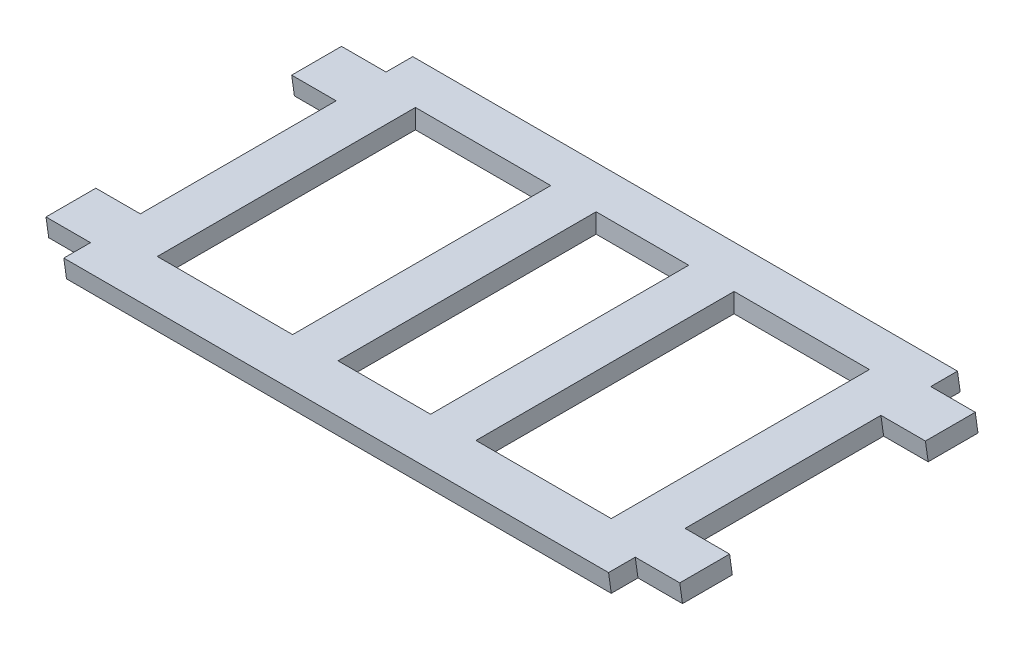
SolidWorks part; units mm, degrees
material "Balsa"
ref_plane "Front Plane" through (0, 0, 0) normal (0, 0, 1) x (1, 0, 0)
ref_plane "Top Plane" through (0, 0, 0) normal (0, 1, 0) x (1, 0, 0)
ref_plane "Right Plane" through (0, 0, 0) normal (1, 0, 0) x (0, 0, -1)
sketch "Sketch1" plane through (0, 0, 0) normal (0, 1, 0) x (1, 0, 0)
  line L4 (0, 0) -> (0, 7.112) construction
  line L5 (0, 7.112) -> (6.35, 7.112)
  line L6 (6.35, 7.112) -> (6.35, 35.052)
  line L7 (6.35, 35.052) -> (0, 35.052)
  line L8 (0, 7.112) -> (0, 0)
  line L10 (6.35, 7.112) -> (84.074, 7.112) construction
  line L11 (84.074, 7.112) -> (90.424, 7.112)
  line L12 (84.074, 7.112) -> (84.074, 35.052)
  line L13 (84.074, 35.052) -> (90.424, 35.052)
  line L15 (90.424, 7.112) -> (90.424, 0)
  line L16 (0, 35.052) -> (0, 42.164)
  line L18 (90.424, 42.164) -> (90.424, 35.052)
  line L19 (0, 42.164) -> (6.35, 42.164)
  line L20 (6.35, 42.164) -> (6.35, 45.974)
  line L21 (90.424, 42.164) -> (84.074, 42.164)
  line L22 (84.074, 42.164) -> (84.074, 45.974)
  line L23 (6.35, 45.974) -> (84.074, 45.974)
  line L24 (0, 0) -> (6.35, 0)
  line L25 (6.35, 0) -> (6.35, -3.81)
  line L26 (90.424, 0) -> (84.074, 0)
  line L27 (84.074, 0) -> (84.074, -3.81)
  line L28 (6.35, -3.81) -> (84.074, -3.81)
  dimension "D1" = 7.112
  dimension "D2" = 90.424
  dimension "D3" = 6.35
  dimension "D4" = 27.94
  dimension "D5" = 77.724
  dimension "D6" = 6.35
  dimension "D7" = 27.94
  dimension "D8" = 7.112
  dimension "D9" = 6.35
  dimension "D10" = 3.81
  dimension "D11" = 6.35
  dimension "D12" = 3.81
  dimension "D13" = 6.35
  dimension "D14" = 3.81
  dimension "D15" = 6.35
  dimension "D16" = 3.81
ref_plane "Plane1" through (0, 2.7668, 0) normal (0, 1, 0) x (1, 0, 0)
sketch "Sketch2" plane through (0, 2.7668, 0) normal (0, 1, 0) x (1, 0, 0)
  line L0 (0, 0) -> (0, -0.3888) construction
  line L2 (90.424, -0.3888) -> (90.424, 6.7232)
  line L3 (90.424, 7.112) -> (90.424, 0) construction
  line L4 (90.424, 6.7232) -> (84.074, 6.7232)
  line L5 (84.074, 6.7232) -> (84.074, 34.6632)
  line L6 (84.074, 7.112) -> (84.074, 35.052) construction
  line L7 (84.074, 34.6632) -> (90.424, 34.6632)
  line L8 (90.424, 34.6632) -> (90.424, 41.7752)
  line L9 (90.424, 42.164) -> (90.424, 35.052) construction
  line L11 (0, 35.052) -> (0, 42.164) construction
  line L12 (0, 41.7752) -> (0, 34.6632)
  line L13 (0, 34.6632) -> (6.35, 34.6632)
  line L14 (6.35, 7.112) -> (6.35, 35.052) construction
  line L15 (6.35, 34.6632) -> (6.35, 6.7232)
  line L16 (6.35, 6.7232) -> (0, 6.7232)
  line L17 (0, 7.112) -> (0, 0) construction
  line L18 (0, 6.7232) -> (0, -0.3888)
  line L19 (0, -0.3888) -> (6.35, -0.3888)
  line L20 (6.35, 0) -> (6.35, -3.81) construction
  line L21 (6.35, -0.3888) -> (6.35, -4.1988)
  line L22 (90.424, -0.3888) -> (84.074, -0.3888)
  line L23 (84.074, 0) -> (84.074, -3.81) construction
  line L24 (84.074, -0.3888) -> (84.074, -4.1988)
  line L25 (6.35, -4.1988) -> (84.074, -4.1988)
  line L26 (0, 41.7752) -> (6.35, 41.7752)
  line L27 (6.35, 41.7752) -> (6.35, 45.5852)
  line L28 (6.35, 42.164) -> (6.35, 45.974) construction
  line L29 (90.424, 41.7752) -> (84.074, 41.7752)
  line L30 (84.074, 41.7752) -> (84.074, 45.5852)
  line L31 (84.074, 42.164) -> (84.074, 45.974) construction
  line L32 (6.35, 45.5852) -> (84.074, 45.5852)
  dimension "D1" = 0.3888
  dimension "D2" = 90.424
  dimension "D3" = 7.112
  dimension "D4" = 6.35
  dimension "D5" = 27.94
  dimension "D6" = 6.35
  dimension "D7" = 7.112
  dimension "D8" = 90.424
  dimension "D9" = 7.112
  dimension "D10" = 6.35
  dimension "D11" = 27.94
  dimension "D12" = 6.35
  dimension "D13" = 7.112
  dimension "D14" = 6.35
  dimension "D15" = 3.81
  dimension "D16" = 6.35
  dimension "D17" = 3.81
  dimension "D18" = 6.35
  dimension "D19" = 3.81
  dimension "D20" = 6.35
  dimension "D21" = 3.81
loft "Loft1" add profiles "Sketch1", "Sketch2" connector at (6.35, 0, -7.112) connector at (6.35, 2.7668, -6.7232)
sketch "Sketch4" plane through (0, 2.7668, 0) normal (0, 1, 0) x (1, 0, 0)
  line L0 (0, 0) -> (90.424, 0) construction
  line L1 (45.212, 0) -> (45.212, 42.164) construction
  line L2 (38.608, 21.082) -> (6.35, 21.082) construction
  line L3 (51.816, 2.667) -> (38.608, 2.667)
  line L4 (51.816, 2.667) -> (51.816, 39.497)
  line L5 (51.816, 39.497) -> (38.608, 39.497)
  line L6 (38.608, 2.667) -> (38.608, 39.497)
  line L7 (51.816, 2.667) -> (38.608, 39.497) construction
  line L8 (51.816, 39.497) -> (38.608, 2.667) construction
  line L9 (51.816, 21.082) -> (84.074, 21.082) construction
  line L10 (32.131, 2.667) -> (12.827, 2.667)
  line L11 (32.131, 2.667) -> (32.131, 39.497)
  line L12 (32.131, 39.497) -> (12.827, 39.497)
  line L13 (12.827, 2.667) -> (12.827, 39.497)
  line L14 (32.131, 2.667) -> (12.827, 39.497) construction
  line L15 (32.131, 39.497) -> (12.827, 2.667) construction
  line L17 (77.597, 2.667) -> (58.293, 2.667)
  line L18 (77.597, 2.667) -> (77.597, 39.497)
  line L19 (77.597, 39.497) -> (58.293, 39.497)
  line L20 (58.293, 2.667) -> (58.293, 39.497)
  line L21 (77.597, 2.667) -> (58.293, 39.497) construction
  line L22 (77.597, 39.497) -> (58.293, 2.667) construction
  point P5 (45.212, 21.082)
  point P12 (22.479, 21.082)
  point P19 (67.945, 21.082)
  dimension "D1" = 90.424
  dimension "D2" = 42.164
  dimension "D3" = 36.83
  dimension "D4" = 13.208
  dimension "D5" = 32.258
  dimension "D6" = 19.304
  dimension "D7" = 36.83
  dimension "D8" = 32.258
  dimension "D9" = 19.304
  dimension "D10" = 36.83
extrude "Cut-Extrude1" cut sketch "Sketch4" against normal blind 7.62
